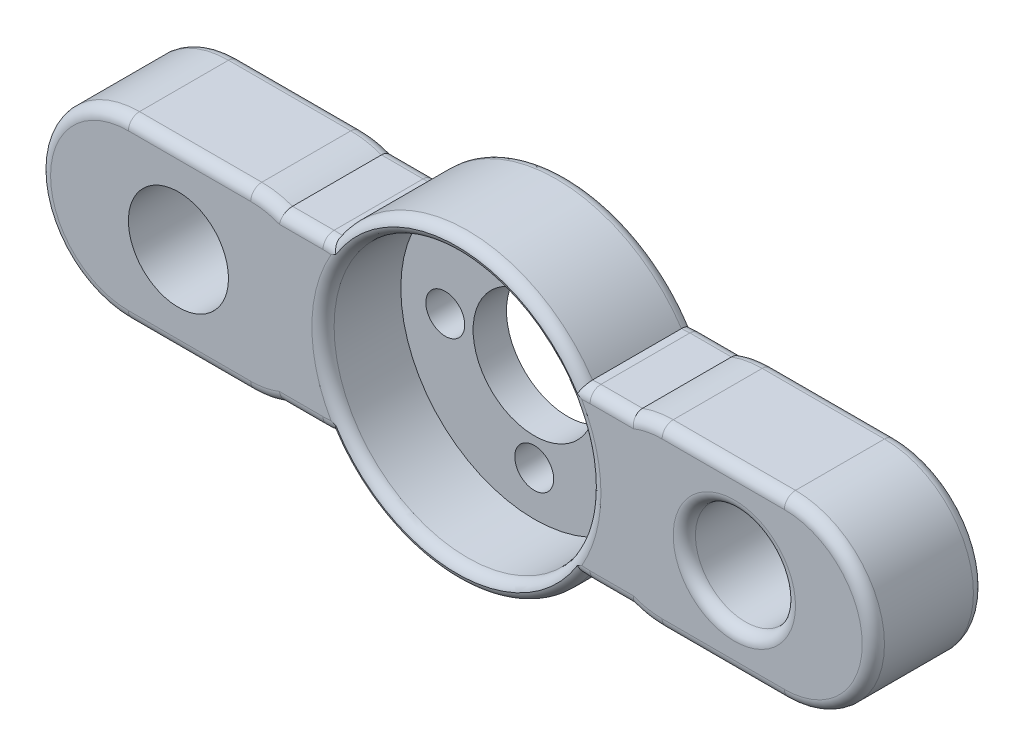
SolidWorks part; units mm, degrees
ref_plane "Plano frontal" through (0, 0, 0) normal (0, 0, 1) x (1, 0, 0)
ref_plane "Plano superior" through (0, 0, 0) normal (0, 1, 0) x (1, 0, 0)
ref_plane "Plano direito" through (0, 0, 0) normal (1, 0, 0) x (0, 0, -1)
sketch "Esboço1" plane through (0, 0, 0) normal (0, 0, 1) x (1, 0, 0)
  line L0 (0, 12) -> (0, -12) construction
  line L1 (-12, 0) -> (-25, 0) construction
  line L2 (-12, -7.5081) -> (-15.738, -7.5081)
  line L3 (-12, 7.5081) -> (-15.738, 7.5081)
  line L4 (9.0002, 0) -> (22.0002, -0.1384) construction
  line L7 (-18.5, 0) -> (-29.5, 0) construction
  line L8 (-18.5, -8) -> (-29.5, -8)
  line L9 (-18.5, 8) -> (-29.5, 8)
  line L10 (12, 7.5081) -> (15.738, 7.5081)
  line L13 (-37.5, 0) -> (-37.5, -13.6342) construction
  line L14 (37.5, -0.2075) -> (37.5, 13.5041) construction
  line L15 (12, -7.5081) -> (15.738, -7.5081)
  line L16 (18.5, 8) -> (29.5, 8)
  line L17 (18.5, -8) -> (29.5, -8)
  line L18 (12, -7.5081) -> (11.2449, -7.47)
  line L19 (12, 7.5081) -> (11.2449, 7.47)
  circle A0 centre (0, 0) radius 5.5
  arc A2 (-12, -7.5081) -> (-11.2449, -7.47) centre (-12, 0) ccw
  arc A6 (-11.2449, 7.47) -> (-12, 7.5081) centre (-12, 0) ccw
  circle A7 centre (-25, 0) radius 4.5
  arc A11 (-11.2449, -7.47) -> (11.2449, -7.47) centre (0, 0) ccw
  arc A12 (11.2449, 7.47) -> (-11.2449, 7.47) centre (0, 0) ccw
  arc A13 (-18.5, -8) -> (-15.738, -7.5081) centre (-18.5, 0) ccw
  arc A14 (-29.5, 8) -> (-29.5, -8) centre (-29.5, 0) ccw
  arc A15 (-15.738, 7.5081) -> (-18.5, 8) centre (-18.5, 0) ccw
  arc A16 (15.738, 7.5081) -> (18.5, 8) centre (18.5, 0) cw
  arc A17 (18.5, -8) -> (15.738, -7.5081) centre (18.5, 0) cw
  circle A18 centre (25, 0) radius 4.5
  arc A19 (29.5, 8) -> (29.5, -8) centre (29.5, 0) cw
  point P8 (-17.0024, 0)
  point P15 (18.9556, -0.106)
  point P20 (-24, 0)
  dimension "D2" = 11
  dimension "D3" = 9
  dimension "D6" = 37.5
  dimension "D7" = 27
  dimension "D5" = 37.5
extrude "Ressalto-extrusão1" add sketch "Esboço1" along normal blind 10
sketch "Esboço2" plane through (0, 0, 10) normal (0, 0, 1) x (1, 0, 0)
  circle A0 centre (0, 0) radius 12
extrude "Corte-extrusão1" cut sketch "Esboço2" against normal blind 7
sketch "Esboço3" plane through (0, 0, 0) normal (0, 0, -1) x (-1, 0, 0)
  circle A0 centre (0, 8) radius 1.75
  dimension "D1" = 3.5
  dimension "D2" = 8
extrude "Corte-extrusão3" cut sketch "Esboço3" against normal blind 8
pattern_circular "PadrãoCircular1" count 4 every 90 about axis through (0, 0, 0) along (0, 0, 1) of "Corte-extrusão3"
fillet "Filete2" radius 1 22 edges at (20.5, 0, 0) (-20.5, 0, 0) (-11.622, 7.4986, 0) (-17.0973, 7.8761, 0) (-24, 8, 0) (-37.5, 0, 0) (-17.0973, -7.8761, 0) (-11.622, -7.4986, 0) (11.6225, 7.4891, 0) (11.6225, -7.4891, 0) (17.0973, -7.8761, 0) (17.0973, 7.8761, 0) (24, -8, 0) (37.5, 0, 0) (-13.869, 7.5081, 0) (-24, -8, 0) (-13.869, -7.5081, 0) (13.869, -7.5081, 0) (0, -13.5, 0) (0, 13.5, 0) (13.869, 7.5081, 0) (24, 8, 0)
fillet "Filete3" radius 1 22 edges at (11.6225, 7.4891, 10) (-11.622, 7.4986, 10) (-13.869, 7.5081, 10) (-17.0973, 7.8761, 10) (-24, 8, 10) (-37.5, 0, 10) (-24, -8, 10) (-17.0973, -7.8761, 10) (-13.869, -7.5081, 10) (-11.622, -7.4986, 10) (0, -13.5, 10) (12, 0, 10) (0, 13.5, 10) (13.869, 7.5081, 10) (17.0973, 7.8761, 10) (24, 8, 10) (20.5, 0, 10) (11.6225, -7.4891, 10) (13.869, -7.5081, 10) (17.0973, -7.8761, 10) (24, -8, 10) (37.5, 0, 10)
